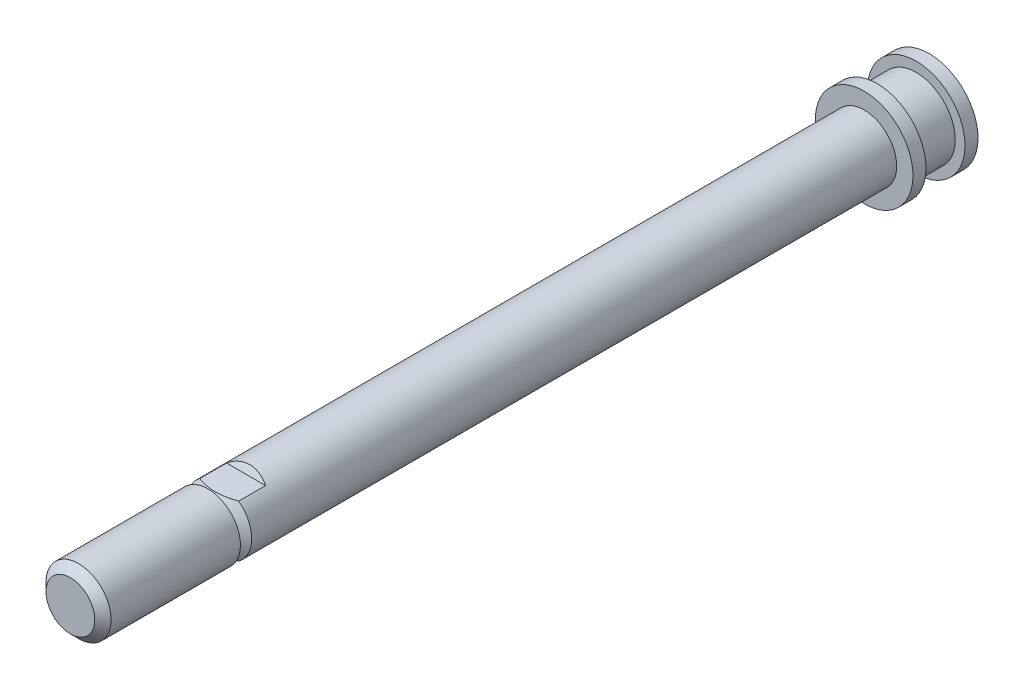
SolidWorks part; units mm, degrees
material "Acciaio in lega"
ref_plane "Piano frontale" through (0, 0, 0) normal (0, 0, 1) x (1, 0, 0)
ref_plane "Piano superiore" through (0, 0, 0) normal (0, 1, 0) x (1, 0, 0)
ref_plane "Piano destro" through (0, 0, 0) normal (1, 0, 0) x (0, 0, -1)
ref_axis "Assi1" through (0, 0, -43.1) along (0, 0, 1)
sketch "Schizzo1" plane through (0, 0, 0) normal (1, 0, 0) x (0, 0, -1)
  line L0 (0, 0) -> (-22, 0)
  line L1 (-22, 5) -> (-22, 0)
  line L2 (-22, 0) -> (-44, 0) construction
  line L3 (-0.866, 5) -> (0, 3.5)
  line L4 (-22, 5) -> (-0.866, 5)
  line L5 (0, 3.5) -> (0.866, 5)
  line L6 (0.866, 5) -> (100, 5)
  line L7 (100, 5) -> (100, 7.5)
  line L8 (100, 7.5) -> (102, 7.5)
  line L9 (110, 7.5) -> (110, 0)
  line L10 (110, 0) -> (0, 0)
  line L11 (108, 7.5) -> (110, 7.5)
  line L12 (102, 6) -> (108, 6)
  line L13 (102, 6) -> (102, 7.5)
  line L15 (108, 6) -> (108, 7.5)
  dimension "D1" = 22
  dimension "D2" = 10
  dimension "D3" = 10
  dimension "D4" = 60
  dimension "D5" = 1.5
  dimension "D6" = 110
  dimension "D7" = 15
  dimension "D8" = 10
  dimension "D9" = 2
  dimension "D10" = 1.5
revolve "Rivoluzione1" add sketch "Schizzo1" angle 360 about L2
chamfer "Smusso1" distance 1.25 angle 45 1 edges at (0, 5, 22)
sketch "Schizzo2" plane through (0, 0, 0) normal (1, 0, 0) x (0, 0, -1)
  line L0 (-22, 5) -> (-0.866, 5) construction
  line L1 (5.5774, 5) -> (0, 5)
  line L2 (5.5774, 5) -> (5, 4)
  line L3 (5, 4) -> (0, 4)
  line L4 (0, 5) -> (0, 4)
  line L5 (5, 0) -> (0, 0) construction
  line L6 (0, -5) -> (0, -4)
  line L7 (5, -4) -> (0, -4)
  line L8 (5.5774, -5) -> (5, -4)
  line L9 (5.5774, -5) -> (0, -5)
  dimension "D1" = 5
  dimension "D2" = 8
  dimension "D3" = 120
extrude "Taglio-Estrusione1" cut sketch "Schizzo2" against normal through all and the other way through all
